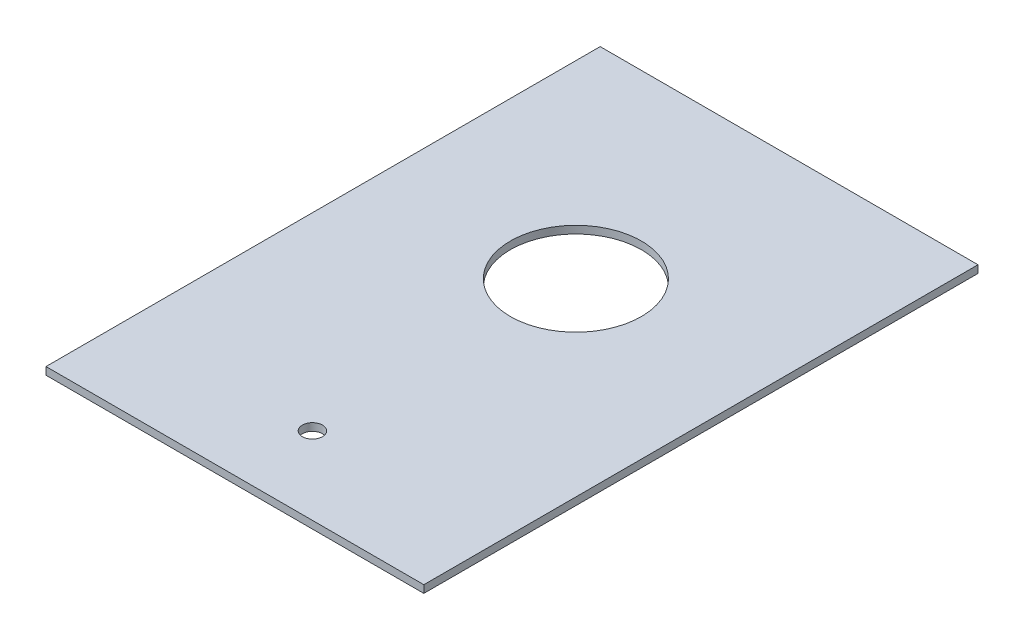
SolidWorks part; units mm, degrees
material "Thornel VCB-20 Carbon Cloth"
ref_plane "Front Plane" through (0, 0, 0) normal (0, 0, 1) x (1, 0, 0)
ref_plane "Top Plane" through (0, 0, 0) normal (0, 1, 0) x (1, 0, 0)
ref_plane "Right Plane" through (0, 0, 0) normal (1, 0, 0) x (0, 0, -1)
sketch "Sketch1" plane through (0, 0, 0) normal (0, 1, 0) x (1, 0, 0)
  line L0 (75, 84.6375) -> (75, -135.3625) construction
  line L1 (-75, -135.3625) -> (75, -135.3625) construction
  line L2 (-75, 84.6375) -> (75, 84.6375) construction
  line L3 (-75, 84.6375) -> (-75, -135.3625) construction
  line L4 (75, 84.6375) -> (75, -135.3625)
  line L5 (-75, -135.3625) -> (75, -135.3625)
  line L6 (-75, 84.6375) -> (75, 84.6375)
  line L7 (-75, 84.6375) -> (-75, -135.3625)
extrude "Boss-Extrude1" add sketch "Sketch1" against normal blind 3
hole_wizard "Hole1" positions "Sketch2" profile "Sketch3" legacy
sketch "Sketch2" plane through (0, 0, 0) normal (0, 1, 0) x (1, 0, 0)
  point P0 (0, 0)
sketch "Sketch3" plane through (0, 0, 0) normal (1, 0, 0) x (0, 0, 1)
  line L0 (0, 0) -> (0, 10)
  line L1 (0, 10) -> (26, 10)
  line L2 (26, 10) -> (26, 0)
  line L3 (26, 0) -> (0, 0)
  line L4 (0, 110) -> (0, -10) construction
  dimension "Diameter" = 52
  dimension "Depth" = 10
hole_wizard "Hole2" positions "Sketch4" profile "Sketch5" legacy
sketch "Sketch4" plane through (0, 0, 0) normal (0, 1, 0) x (1, 0, 0)
  point P0 (0, -104.6)
sketch "Sketch5" plane through (0, 0, 104.6) normal (1, 0, 0) x (0, 0, 1)
  line L0 (0, 0) -> (0, 100)
  line L1 (0, 100) -> (4, 100)
  line L2 (4, 100) -> (4, 0)
  line L3 (4, 0) -> (0, 0)
  line L4 (0, 110) -> (0, -10) construction
  dimension "Diameter" = 8
  dimension "Depth" = 100
